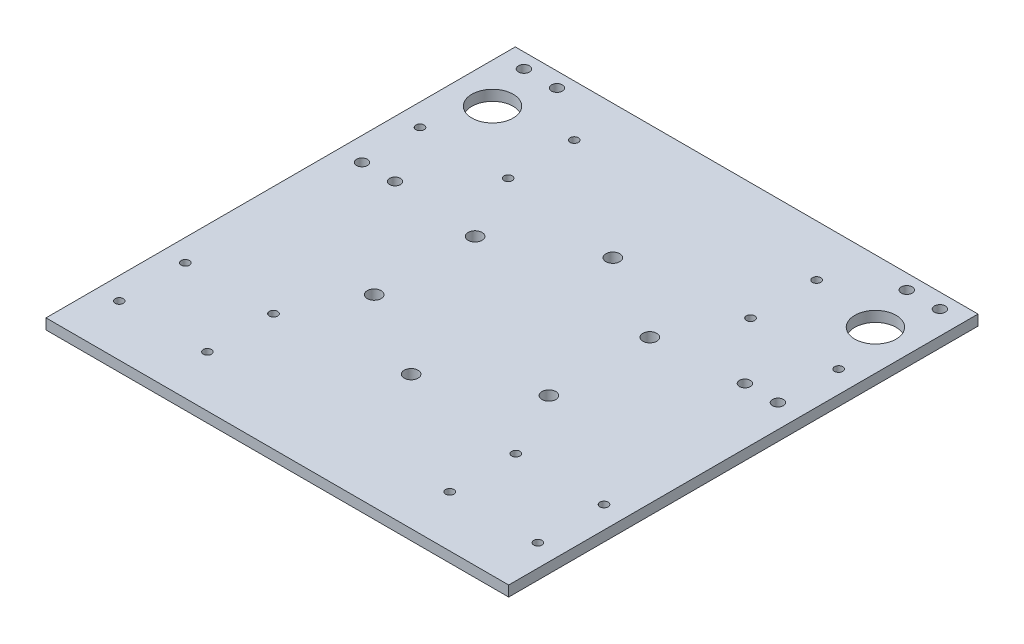
SolidWorks part; units mm, degrees
ref_plane "Front Plane" through (0, 0, 0) normal (0, 0, 1) x (1, 0, 0)
ref_plane "Top Plane" through (0, 0, 0) normal (0, 1, 0) x (1, 0, 0)
ref_plane "Right Plane" through (0, 0, 0) normal (1, 0, 0) x (0, 0, -1)
sketch "Sketch1" plane through (0, 0, 0) normal (0, 1, 0) x (1, 0, 0)
  line L1 (-70, -71) -> (70, -71)
  line L2 (-70, -71) -> (-70, 71)
  line L3 (-70, 71) -> (70, 71)
  line L4 (70, -71) -> (70, 71)
  line L5 (-70, -71) -> (70, 71) construction
  line L6 (-70, 71) -> (70, -71) construction
  point P0 (0, 0)
  dimension "D1" = 140
  dimension "D2" = 142
extrude "Boss-Extrude1" add sketch "Sketch1" along normal blind 3.175
sketch "Sketch2" plane through (0, 3.175, 0) normal (0, 1, 0) x (1, 0, 0)
  line L0 (-45, 30.5) -> (-30, 30.5) construction
  line L1 (-45, -30.5) -> (45, -30.5) construction
  line L2 (-45, -30.5) -> (-45, 30.5) construction
  line L3 (-45, 30.5) -> (45, 30.5) construction
  line L4 (45, -30.5) -> (45, 30.5) construction
  line L5 (-45, -30.5) -> (45, 30.5) construction
  line L6 (-45, 30.5) -> (45, -30.5) construction
  line L7 (-30, 30.5) -> (-30, 60.5) construction
  line L8 (-70, 71) -> (-70, -71) construction
  line L9 (-30, 60.5) -> (-70, 60.5) construction
  line L10 (-30, 60.5) -> (-30, 30.5) construction
  line L11 (-30, 30.5) -> (-70, 30.5) construction
  line L12 (-70, 60.5) -> (-70, 30.5) construction
  line L13 (-30, 60.5) -> (-70, 30.5) construction
  line L14 (-30, 30.5) -> (-70, 60.5) construction
  line L15 (-51.4643, -23.9643) -> (-51.4643, 60.5) construction
  line L16 (-70, 45.5) -> (-30, 45.5) construction
  line L17 (-50, 60.5) -> (-50, 30.5) construction
  line L18 (-57.9286, 52.0357) -> (-57.9286, 62.0357) construction
  line L19 (-62.9286, 66.5357) -> (-52.9286, 66.5357) construction
  line L20 (-67.9286, 62.0357) -> (-47.9286, 62.0357) construction
  line L21 (-67.9286, 62.0357) -> (-67.9286, 22.0357) construction
  line L22 (-67.9286, 22.0357) -> (-47.9286, 22.0357) construction
  line L23 (-47.9286, 62.0357) -> (-47.9286, 22.0357) construction
  line L24 (-67.9286, 62.0357) -> (-47.9286, 22.0357) construction
  line L25 (-67.9286, 22.0357) -> (-47.9286, 62.0357) construction
  line L26 (-67.9286, 17.5357) -> (-47.9286, 17.5357) construction
  line L27 (-67.9286, 17.5357) -> (-67.9286, 66.5357) construction
  line L28 (-67.9286, 66.5357) -> (-47.9286, 66.5357) construction
  line L29 (-47.9286, 17.5357) -> (-47.9286, 66.5357) construction
  line L30 (-67.9286, 17.5357) -> (-47.9286, 66.5357) construction
  line L31 (-67.9286, 66.5357) -> (-47.9286, 17.5357) construction
  line L32 (-67.9286, 14.0357) -> (-47.9286, 14.0357) construction
  line L33 (-67.9286, 14.0357) -> (-67.9286, 70.0357) construction
  line L34 (-67.9286, 70.0357) -> (-47.9286, 70.0357) construction
  line L35 (-47.9286, 14.0357) -> (-47.9286, 70.0357) construction
  line L36 (-67.9286, 14.0357) -> (-47.9286, 70.0357) construction
  line L37 (-67.9286, 70.0357) -> (-47.9286, 14.0357) construction
  line L38 (-67.9286, 42.0357) -> (-47.9286, 42.0357) construction
  line L39 (0, -55) -> (0, 55) construction
  line L40 (-45, 30.5) -> (-45, 45.5) construction
  line L41 (-55, 0) -> (55, 0) construction
  line L42 (-67.9286, 52.0357) -> (-30, 52.0357) construction
  circle A0 centre (-45, 0) radius 6.4643 construction
  circle A1 centre (-57.9286, 52.0357) radius 6.4643 construction
  circle A2 centre (-57.9286, 52.0357) radius 6.25
  circle A8 centre (-57.9286, 52.0357) radius 2.45 construction
  circle A9 centre (-62.9286, 66.5357) radius 1.65
  circle A10 centre (-52.9286, 66.5357) radius 1.65
  circle A11 centre (-52.9286, 17.5357) radius 1.65
  circle A12 centre (-62.9286, 17.5357) radius 1.65
  circle A13 centre (52.9286, 17.5357) radius 1.65
  circle A14 centre (62.9286, 17.5357) radius 1.65
  circle A15 centre (57.9286, 52.0357) radius 6.25
  circle A16 centre (52.9286, 66.5357) radius 1.65
  circle A17 centre (62.9286, 66.5357) radius 1.65
  circle A18 centre (-36.6667, 55.5) radius 1.25
  circle A19 centre (-36.6667, 35.5) radius 1.25
  circle A20 centre (-63.3333, 35.5) radius 1.25
  circle A21 centre (-63.3333, 55.5) radius 1.25 construction
  circle A22 centre (36.6667, 35.5) radius 1.25
  circle A23 centre (63.3333, 35.5) radius 1.25
  circle A24 centre (36.6667, 55.5) radius 1.25
  circle A25 centre (63.3333, 55.5) radius 1.25 construction
  circle A26 centre (63.3333, -35.5) radius 1.25
  circle A27 centre (36.6667, -35.5) radius 1.25
  circle A28 centre (63.3333, -55.5) radius 1.25
  circle A29 centre (36.6667, -55.5) radius 1.25
  circle A30 centre (-36.6667, -35.5) radius 1.25
  circle A31 centre (-63.3333, -35.5) radius 1.25
  circle A32 centre (-36.6667, -55.5) radius 1.25
  circle A33 centre (-63.3333, -55.5) radius 1.25
  point P0 (0, 0)
  point P10 (-50, 45.5)
  point P25 (-57.9286, 42.0357)
  point P31 (-57.9286, 42.0357)
  point P32 (-57.9286, 62.0357)
  point P37 (-57.9286, 42.0357)
  point P44 (-57.9286, 66.5357)
  point P45 (-57.9286, 66.5357)
  dimension "D5" = 12.9286
  dimension "D6" = 12.9286
  dimension "D7" = 12.5
  dimension "D8" = 4.9
  dimension "D14" = 10
  dimension "D9" = 10
  dimension "D15" = 3.3
  dimension "D16" = 2.5
  dimension "D1" = 90
  dimension "D2" = 61
  dimension "D3" = 15
  dimension "D4" = 30
  dimension "D10" = 20
  dimension "D11" = 40
  dimension "D12" = 49
  dimension "D13" = 56
  dimension "D17" = 5
  dimension "D18" = 8.4643
sketch "Sketch4" plane through (0, 3.175, 0) normal (0, 1, 0) x (1, 0, 0)
  line L0 (0, 0) -> (0, 30.525) construction
  line L1 (0, 0) -> (26.4354, 15.2625) construction
  circle A0 centre (0, 0) radius 40 construction
  circle A1 centre (0, 0) radius 30.525 construction
  circle A2 centre (0, 30.525) radius 2.1
  circle A3 centre (26.4354, 15.2625) radius 2.1
  circle A4 centre (26.4354, -15.2625) radius 2.1
  circle A5 centre (0, -30.525) radius 2.1
  circle A6 centre (-26.4354, -15.2625) radius 2.1
  circle A7 centre (-26.4354, 15.2625) radius 2.1
  dimension "D1" = 80
  dimension "D2" = 61.05
  dimension "D3" = 4.2
  dimension "D5" = 60
  dimension "D4" = 6
extrude "Cut-Extrude1" cut sketch "Sketch2" against normal up to surface (3.175 mm away) contours A9 | A10 | A18 | A2 | A19 | A20 | A11 | A12 | A16 | A17 | A24 | A15 | A23 | A22 | A13 | A14 | A31 | A30 | A33 | A32 | A27 | A26 | A29 | A28 up to face at (0, 0, 0)
extrude "Cut-Extrude2" cut sketch "Sketch4" against normal up to surface (3.175 mm away) contours A7 | A2 | A3 | A6 | A4 | A5 up to face at (57.9286, 0, -58.2857)
